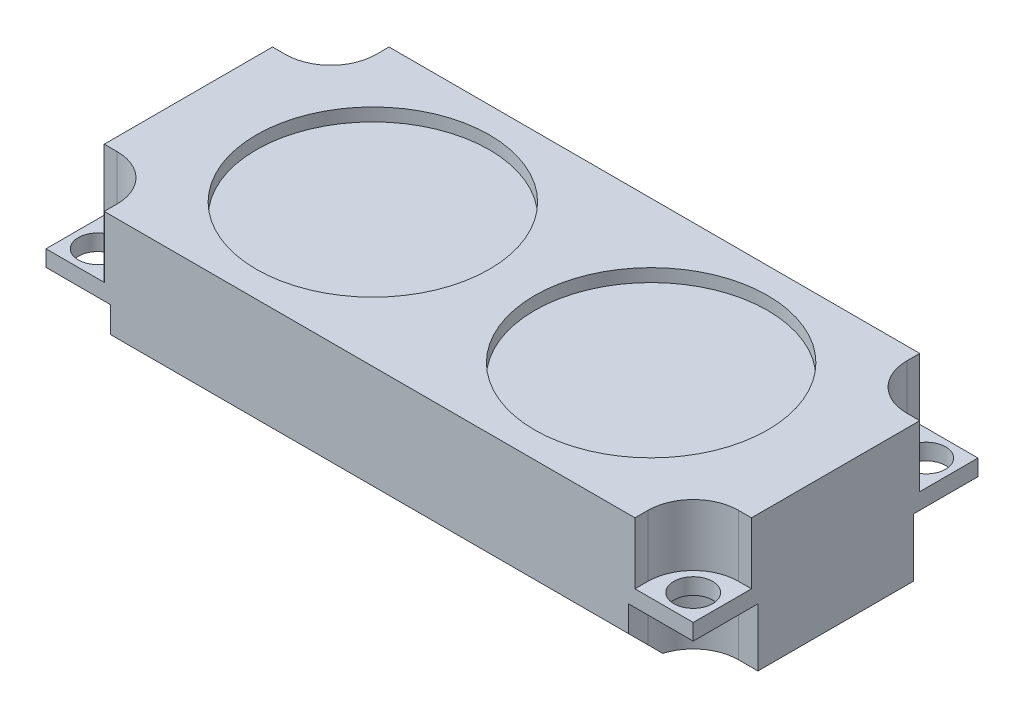
SolidWorks part; units mm, degrees
ref_plane "前视基准面" through (0, 0, 0) normal (0, 0, 1) x (1, 0, 0)
ref_plane "上视基准面" through (0, 0, 0) normal (0, 1, 0) x (1, 0, 0)
ref_plane "右视基准面" through (0, 0, 0) normal (1, 0, 0) x (0, 0, -1)
sketch "草图1" plane through (0, 0, 0) normal (0, 1, 0) x (1, 0, 0)
  line L1 (0, 0) -> (100, 0)
  line L2 (0, 0) -> (0, 44)
  line L3 (0, 44) -> (100, 44)
  line L4 (100, 0) -> (100, 44)
  dimension "D1" = 100
  dimension "D2" = 44
extrude "凸台-拉伸1" add sketch "草图1" along normal blind 21
chamfer "倒角1" distance 5 angle 45 2 edges at (50, 0, -44) (50, 0, 0)
sketch "草图2" plane through (0, 21, 0) normal (0, 1, 0) x (1, 0, 0)
  line L0 (50, 44) -> (50, 0) construction
  line L1 (100, 44) -> (0, 44) construction
  line L2 (0, 0) -> (100, 0) construction
  line L3 (100, 22) -> (0, 22) construction
  line L4 (100, 0) -> (100, 44) construction
  line L5 (0, 44) -> (0, 0) construction
  circle A0 centre (96, 4) radius 3
  circle A1 centre (4, 4) radius 3
  circle A2 centre (4, 40) radius 3
  circle A3 centre (96, 40) radius 3
  dimension "D1" = 6
  dimension "D2" = 4
  dimension "D3" = 4
extrude "切除-拉伸1" cut sketch "草图2" against normal through all
sketch "草图3" plane through (0, 21, 0) normal (0, 1, 0) x (1, 0, 0)
  line L0 (50, 44) -> (50, 0) construction
  line L1 (100, 0) -> (91, 0)
  line L2 (100, 0) -> (100, 9)
  line L3 (100, 9) -> (91, 9)
  line L4 (91, 0) -> (91, 9)
  line L5 (100, 44) -> (0, 44) construction
  line L6 (0, 0) -> (100, 0) construction
  line L7 (100, 22) -> (0, 22) construction
  line L8 (100, 0) -> (100, 44) construction
  line L9 (0, 44) -> (0, 0) construction
  line L10 (9, 0) -> (9, 9)
  line L11 (0, 9) -> (9, 9)
  line L12 (0, 0) -> (0, 9)
  line L13 (0, 0) -> (9, 0)
  line L14 (91, 44) -> (91, 35)
  line L15 (100, 35) -> (91, 35)
  line L16 (100, 44) -> (100, 35)
  line L17 (100, 44) -> (91, 44)
  line L18 (0, 44) -> (9, 44)
  line L19 (0, 44) -> (0, 35)
  line L20 (0, 35) -> (9, 35)
  line L21 (9, 44) -> (9, 35)
  dimension "D1" = 9
  dimension "D2" = 9
extrude "切除-拉伸2" cut sketch "草图3" against normal blind 9.5
sketch "草图4" plane through (0, 21, 0) normal (0, 1, 0) x (1, 0, 0)
  line L0 (50, 44) -> (50, 0) construction
  line L1 (91, 44) -> (9, 44) construction
  line L2 (9, 0) -> (91, 0) construction
  line L3 (0, 22) -> (100, 22) construction
  line L4 (0, 35) -> (0, 9) construction
  line L5 (100, 9) -> (100, 35) construction
  circle A0 centre (28.5, 22) radius 18
  circle A1 centre (71.5, 22) radius 18
  dimension "D1" = 36
  dimension "D2" = 43
extrude "切除-拉伸3" cut sketch "草图4" against normal blind 2
sketch "草图5" plane through (0, 0, 0) normal (0, -1, 0) x (1, 0, 0)
  line L0 (0, -22) -> (100, -22) construction
  line L1 (0, -39) -> (0, -5) construction
  line L2 (100, -5) -> (100, -39) construction
  line L3 (50, -5) -> (50, -39) construction
  line L4 (93.1716, -5) -> (6.8284, -5) construction
  line L5 (6.8284, -39) -> (93.1716, -39) construction
  line L6 (90, -44) -> (90, -34)
  line L7 (100, 0) -> (90, 0)
  line L8 (100, 0) -> (100, -10)
  line L9 (100, -10) -> (90, -10)
  line L10 (90, 0) -> (90, -10)
  line L11 (100, -34) -> (90, -34)
  line L12 (100, -44) -> (100, -34)
  line L13 (100, -44) -> (90, -44)
  line L14 (10, 0) -> (10, -10)
  line L15 (0, -10) -> (10, -10)
  line L16 (0, 0) -> (0, -10)
  line L17 (0, 0) -> (10, 0)
  line L18 (0, -44) -> (10, -44)
  line L19 (0, -44) -> (0, -34)
  line L20 (0, -34) -> (10, -34)
  line L21 (10, -44) -> (10, -34)
  dimension "D1" = 10
  dimension "D2" = 10
extrude "切除-拉伸4" cut sketch "草图5" against normal blind 9
fillet "圆角1" radius 7 8 edges at (9, 16.25, -35) (9, 16.25, -9) (10, 4.5, -10) (10, 4.5, -34) (91, 16.25, -35) (90, 4.5, -34) (91, 16.25, -9) (90, 4.5, -10)
